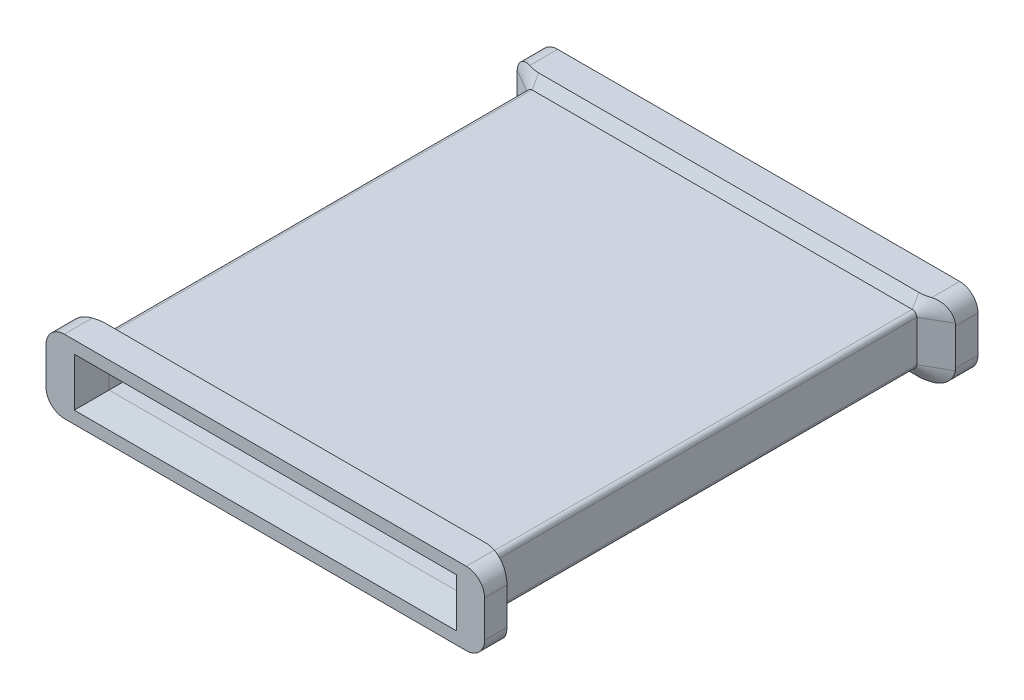
SolidWorks part; units mm, degrees
material "ABS"
ref_plane "Front Plane" through (0, 0, 0) normal (0, 0, 1) x (1, 0, 0)
ref_plane "Top Plane" through (0, 0, 0) normal (0, 1, 0) x (1, 0, 0)
ref_plane "Right Plane" through (0, 0, 0) normal (1, 0, 0) x (0, 0, -1)
sketch "Sketch1" plane through (0, 0, 0) normal (0, 0, 1) x (1, 0, 0)
  line L0 (0, 8) -> (48, 8)
  line L3 (48, 8) -> (48, 0)
  line L4 (48, 0) -> (0, 0)
  line L5 (0, 0) -> (0, 8)
  line L9 (3.4, 6.35) -> (44.6, 6.35)
  line L10 (3.4, 6.35) -> (3.4, 1.65)
  line L11 (3.4, 1.65) -> (44.6, 1.65)
  line L12 (44.6, 6.35) -> (44.6, 1.65)
  dimension "D1" = 1.65
  dimension "D2" = 41.2
  dimension "D4" = 4.7
  dimension "D5" = 1.65
  dimension "D7" = 3.4
  dimension "D8" = 3.4
extrude "Boss-Extrude1" add sketch "Sketch1" along normal blind 54
sketch "Sketch2" plane through (0, 0, 54) normal (0, 0, 1) x (1, 0, 0)
  line L1 (3.2, 6.75) -> (44.8, 6.75)
  line L2 (2.7, 6.25) -> (2.7, 1.75)
  line L3 (3.2, 1.25) -> (44.8, 1.25)
  line L4 (45.3, 6.25) -> (45.3, 1.75)
  line L5 (3.4, 1.65) -> (44.6, 1.65) construction
  line L6 (44.6, 6.35) -> (3.4, 6.35) construction
  line L8 (3.4, 6.35) -> (3.4, 1.65) construction
  line L9 (44.6, 1.65) -> (44.6, 6.35) construction
  arc A0 (2.7, 1.75) -> (3.2, 1.25) centre (3.2, 1.75) ccw
  arc A1 (44.8, 1.25) -> (45.3, 1.75) centre (44.8, 1.75) ccw
  arc A2 (44.8, 6.75) -> (45.3, 6.25) centre (44.8, 6.25) cw
  arc A3 (3.2, 6.75) -> (2.7, 6.25) centre (3.2, 6.25) ccw
  dimension "D1" = 0.5
  dimension "D2" = 0.4
  dimension "D3" = 0.7
  dimension "D4" = 0.7
  dimension "D5" = 0.4
extrude "Cut-Extrude1" cut sketch "Sketch2" against normal offset from surface (50 mm away) 2 from offset 2 flip side to cut up to face at (24, 4, 0) offset against normal yes
fillet "Fillet1" radius 2 8 edges at (48, 8, 53) (48, 0, 53) (48, 0, 1) (48, 8, 1) (0, 0, 1) (0, 8, 1) (0, 0, 53) (0, 8, 53)
chamfer "Chamfer4" distance 2 angle 60 16 edges at (2.7, 4, 52) (2.8464, 1.3964, 52) (2.8464, 6.6036, 52) (24, 1.25, 52) (24, 6.75, 52) (45.1536, 1.3964, 52) (45.1536, 6.6036, 52) (45.3, 4, 52) (2.7, 4, 2) (2.8464, 1.3964, 2) (2.8464, 6.6036, 2) (24, 1.25, 2) (24, 6.75, 2) (45.1536, 1.3964, 2) (45.1536, 6.6036, 2) (45.3, 4, 2) first distance on face at (2.7, 4, 27) first distance on face at (2.8982, 1.4482, 27) first distance on face at (2.8982, 6.5518, 27) first distance on face at (24, 1.25, 27) first distance on face at (24, 6.75, 27) first distance on face at (45.1018, 1.4482, 27) first distance on face at (45.1018, 6.5518, 27) first distance on face at (45.3, 4, 27)
chamfer "Chamfer5" distance 3.5 angle 5 8 edges at (44.6, 4, 54) (24, 1.65, 54) (3.4, 4, 54) (24, 6.35, 54) (44.6, 4, 0) (24, 1.65, 0) (3.4, 4, 0) (24, 6.35, 0) first distance on face at (44.6, 4, 27) first distance on face at (24, 1.65, 27) first distance on face at (3.4, 4, 27) first distance on face at (24, 6.35, 27)
